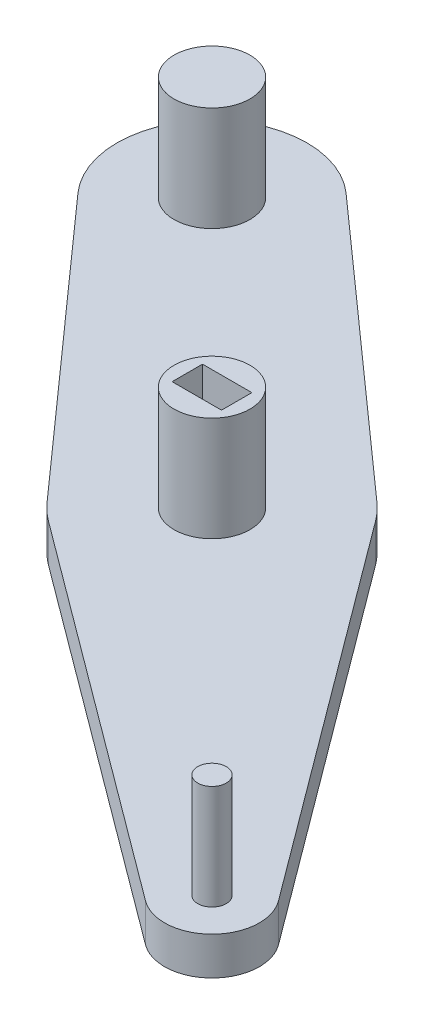
SolidWorks part; units mm, degrees
ref_plane "Front Plane" through (0, 0, 0) normal (0, 0, 1) x (1, 0, 0)
ref_plane "Top Plane" through (0, 0, 0) normal (0, 1, 0) x (1, 0, 0)
ref_plane "Right Plane" through (0, 0, 0) normal (1, 0, 0) x (0, 0, -1)
sketch "Sketch1" plane through (0, 0, 0) normal (0, 1, 0) x (1, 0, 0)
  line L0 (-35.3553, 42.8553) -> (0, 7.5) construction
  line L1 (-60, 15) -> (60, 15) construction
  line L2 (-60, 15) -> (-60, -15) construction
  line L3 (-60, -15) -> (60, -15) construction
  line L4 (60, 15) -> (60, -15) construction
  line L5 (0, -15) -> (0, 15) construction
  line L6 (-60, 0) -> (60, 0) construction
  line L7 (0, 7.5) -> (6.364, 1.136) construction
  line L8 (-35.3553, 42.8553) -> (-63.6396, 71.1396) construction
  line L9 (-35.3553, 42.8553) -> (-68.1214, 65.7984) construction
  line L10 (-76.3129, 71.5342) -> (5.6023, 14.1765) construction
  line L11 (-36.2947, 57.8259) -> (-62.7003, 56.1691) construction
  line L12 (60, 0) -> (60, 87.9663) construction
  line L13 (0, 0) -> (0, 23.1228) construction
  line L14 (-60, 15) -> (-60, 265) construction
  line L15 (-60, 2.7) -> (60, 2.7) construction
  line L16 (72.3, 15) -> (72.3, 115) construction
  line L17 (72.3, 115) -> (-50, 130) construction
  line L18 (-50, 130) -> (-50, 270) construction
  line L19 (-50, 270) -> (-70, 270) construction
  line L20 (-70, 270) -> (-70, 130) construction
  line L21 (-70, 130) -> (-148.2043, 78.9057) construction
  line L22 (-147.7406, 53.4998) -> (-66.3473, 4.4643) construction
  line L23 (-42.6897, 32.9813) -> (-2.9815, 3.4862)
  line L24 (-25.4813, 50.1897) -> (4.0138, 10.4815)
  line L25 (-71.1056, 64.4868) -> (-44.5385, 34.6724)
  line L26 (-56.9868, 78.6056) -> (-27.1724, 52.0385)
  circle A0 centre (-60, 15) radius 15 construction
  circle A1 centre (-60, -15) radius 15 construction
  circle A2 centre (60, 15) radius 15 construction
  circle A3 centre (60, -15) radius 15 construction
  circle A4 centre (0, -15) radius 15 construction
  circle A5 centre (0, 7.5) radius 7.5 construction
  circle A6 centre (-35.3553, 42.8553) radius 50 construction
  circle A7 centre (6.364, 51.136) radius 50 construction
  circle A8 centre (-35.3553, 42.8553) radius 15 construction
  circle A9 centre (-63.6396, 71.1396) radius 15 construction
  circle A10 centre (-68.1214, 65.7984) radius 15 construction
  circle A11 centre (-140, 66.3483) radius 15 construction
  circle A15 centre (0, 20) radius 5 construction
  circle A16 centre (0, 30) radius 5 construction
  circle A17 centre (-140, 66.3483) radius 9.3 construction
  circle A18 centre (-60, 15) radius 9.3 construction
  circle A19 centre (60, 15) radius 9.3 construction
  circle A20 centre (-35.3553, 42.8553) radius 9.3 construction
  circle A21 centre (6.364, 51.136) radius 9.3 construction
  circle A22 centre (-60, 265) radius 1.6 construction
  circle A23 centre (-140, 66.3483) radius 12.3 construction
  circle A24 centre (-60, 15) radius 12.3 construction
  circle A25 centre (-35.3553, 42.8553) radius 12.3 construction
  circle A26 centre (6.364, 51.136) radius 12.3 construction
  circle A27 centre (60, 15) radius 12.3 construction
  arc A28 (60, 2.7) -> (72.3, 15) centre (60, 15) ccw construction
  arc A29 (-148.2043, 78.9057) -> (-147.7406, 53.4998) centre (-140, 66.3483) ccw construction
  arc A30 (-66.3473, 4.4643) -> (-60, 2.7) centre (-60, 15) ccw construction
  circle A31 centre (0, 7.5) radius 5 construction
  arc A32 (-2.9815, 3.4862) -> (4.0138, 10.4815) centre (0, 7.5) ccw
  circle A33 centre (-63.6396, 71.1396) radius 10 construction
  arc A34 (-71.1056, 64.4868) -> (-56.9868, 78.6056) centre (-63.6396, 71.1396) cw
  arc A35 (-44.5385, 34.6724) -> (-42.6897, 32.9813) centre (-35.3553, 42.8553) ccw
  arc A36 (-27.1724, 52.0385) -> (-25.4813, 50.1897) centre (-35.3553, 42.8553) cw
  circle A37 centre (0, 7.5) radius 1.5
  circle A38 centre (-35.3553, 42.8553) radius 4
  circle A39 centre (-63.6396, 71.1396) radius 4
  point P0 (0, 0)
  point P24 (-35.3553, 42.8553)
  dimension "D3" = 30
  dimension "D4" = 15
  dimension "D5" = 100
  dimension "D8" = 100
  dimension "D9" = 30
  dimension "D12" = 30
  dimension "D14" = 30
  dimension "D17" = 10
  dimension "D18" = 10
  dimension "D19" = 42.5332
  dimension "D20" = 250
  dimension "D21" = 3.2
  dimension "D22" = 18.6
  dimension "D30" = 10
  dimension "D31" = 20
  dimension "D32" = 3
  dimension "D33" = 8
  dimension "D34" = 8
  dimension "D1" = 120
  dimension "D2" = 30
  dimension "D6" = 45
  dimension "D7" = 9
  dimension "D10" = 40
  dimension "D11" = 360
  dimension "D13" = 10
  dimension "D15" = 15
  dimension "D16" = 80
  dimension "D24" = 10
  dimension "D25" = 10
  dimension "D26" = 5
  dimension "D27" = 140
  dimension "D28" = 140
  dimension "D29" = 100
  dimension "D23" = 3
extrude "Boss-Extrude1" add sketch "Sketch1" along normal blind 4 contours A39 | A36 L26 A34 L25 A35 L23 A32 L24 A39 A38 A37 | A38 | A37 | A38 | A39 | L24 A32 L23 A35 L25 A34 L26 A36 region at (-42.9066, 0, -34.6003) region at (0, 0, -7.5) region at (-35.3553, 0, -42.8553) region at (-63.6396, 0, -71.1396)
extrude "Boss-Extrude2" add sketch "Sketch1<5>" along normal blind 11 from offset 4 contours A39 | A38 | A37 region at (-35.3553, 0, -42.8553) region at (-63.6396, 0, -71.1396)
sketch "Sketch1<5>" plane through (0, 0, 0) normal (0, 1, 0) x (1, 0, 0) same geometry as "Sketch1"
sketch "Sketch4" plane through (0, 15, 0) normal (0, 1, 0) x (1, 0, 0)
  line L1 (-37.9553, 41.2553) -> (-32.7553, 41.2553)
  line L2 (-37.9553, 41.2553) -> (-37.9553, 44.4553)
  line L3 (-37.9553, 44.4553) -> (-32.7553, 44.4553)
  line L4 (-32.7553, 41.2553) -> (-32.7553, 44.4553)
  line L5 (-35.3553, 44.4553) -> (-35.3553, 41.2553) construction
  line L6 (-37.9553, 42.8553) -> (-32.7553, 42.8553) construction
  point P0 (-35.3553, 42.8553)
  dimension "D1" = 3.2
  dimension "D2" = 5.2
extrude "Cut-Extrude1" cut sketch "Sketch4" against normal through all
